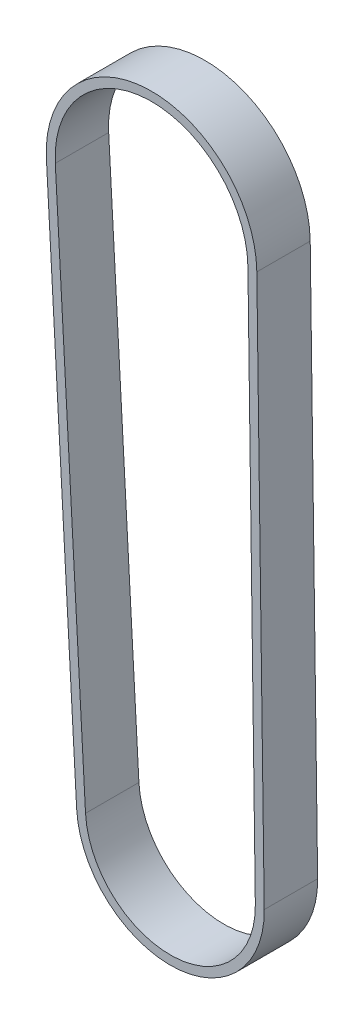
SolidWorks part; units mm, degrees
ref_plane "Front Plane" through (0, 0, 0) normal (0, 0, 1) x (1, 0, 0)
ref_plane "Top Plane" through (0, 0, 0) normal (0, 1, 0) x (1, 0, 0)
ref_plane "Right Plane" through (0, 0, 0) normal (1, 0, 0) x (0, 0, -1)
sketch "Sketch2" plane through (0, 0, 0) normal (0, 0, 1) x (1, 0, 0)
  line L0 (0, 0) -> (1, 0) construction
  line L1 (0, 0) -> (0, 1) construction
  line L6 (-11.1272, -93.2351) -> (-16.2253, -0.8958)
  line L7 (16.2485, 0.2195) -> (17.4976, -92.252)
  arc A2 (17.4976, -92.252) -> (-11.1272, -93.2351) centre (3.175, -92.4455) cw
  arc A3 (-16.2253, -0.8958) -> (16.2485, 0.2195) centre (0, 0) cw
extrude "Extrude-Thin1" add sketch "Sketch2" against normal blind 9 thin thin type one direction wall 1.5
